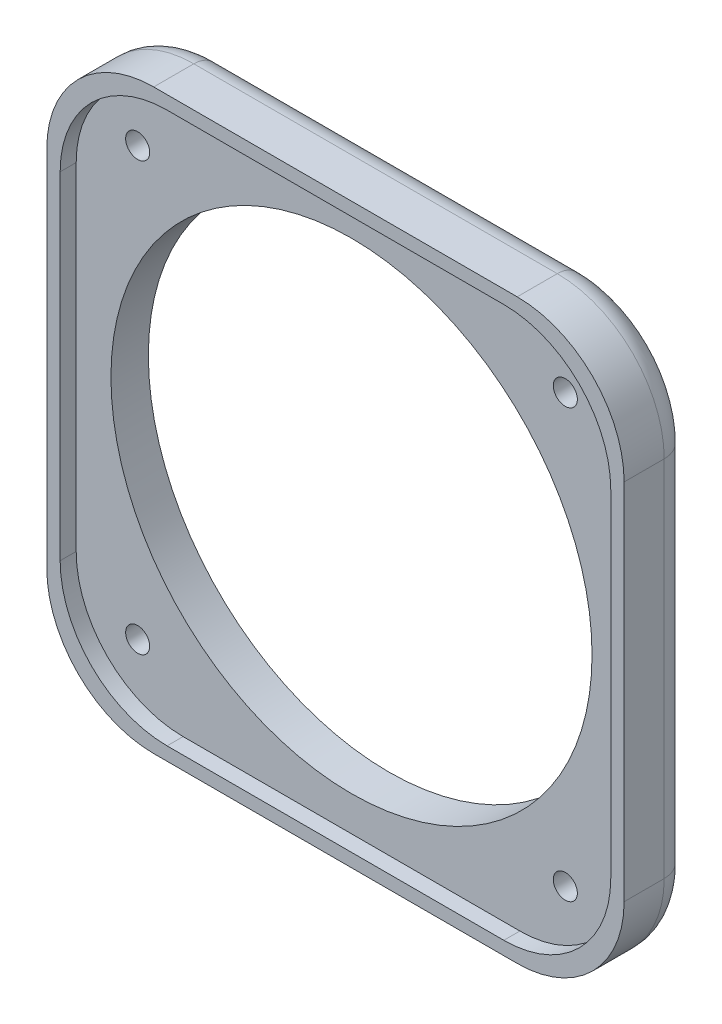
SolidWorks part; units mm, degrees
ref_plane "Plan de face" through (0, 0, 0) normal (0, 0, 1) x (1, 0, 0)
ref_plane "Plan de dessus" through (0, 0, 0) normal (0, 1, 0) x (1, 0, 0)
ref_plane "Plan de droite" through (0, 0, 0) normal (1, 0, 0) x (0, 0, -1)
sketch "Esquisse1" plane through (0, 0, 0) normal (0, 0, 1) x (1, 0, 0)
  line L1 (20, 0) -> (88, 0)
  line L2 (0, -20) -> (0, -88)
  line L3 (20, -108) -> (88, -108)
  line L4 (108, -20) -> (108, -88)
  arc A0 (0, -88) -> (20, -108) centre (20, -88) ccw
  arc A1 (88, -108) -> (108, -88) centre (88, -88) ccw
  arc A2 (88, 0) -> (108, -20) centre (88, -20) cw
  arc A3 (20, 0) -> (0, -20) centre (20, -20) ccw
  circle A4 centre (54, -54) radius 45
  circle A5 centre (14, -14) radius 2.25
  circle A6 centre (94, -14) radius 2.25
  circle A7 centre (94, -94) radius 2.25
  circle A8 centre (14, -94) radius 2.25
  point P7 (0, -108)
  point P12 (108, 0)
  point P15 (0, 0)
  point P18 (54, 0)
  point P19 (108, -54)
  dimension "D3" = 20
  dimension "D4" = 90
  dimension "D7" = 4.5
  dimension "D8" = 4.5
  dimension "D9" = 4.5
  dimension "D10" = 4.5
  dimension "D1" = 108
  dimension "D2" = 108
  dimension "D5" = 54
  dimension "D6" = 54
  dimension "D11" = 80
  dimension "D12" = 80
  dimension "D13" = 80
  dimension "D14" = 80
  dimension "D15" = 14
  dimension "D16" = 14
  dimension "D17" = 14
  dimension "D18" = 14
  dimension "D19" = 14
  dimension "D20" = 14
extrude "Boss.-Extru.1" add sketch "Esquisse1" along normal blind 7
sketch "Esquisse2" plane through (0, 0, 7) normal (0, 0, 1) x (1, 0, 0)
  line L0 (108, -88) -> (108, -20) construction
  line L1 (20, 0) -> (88, 0)
  line L2 (0, -20) -> (0, -88)
  line L3 (20, -108) -> (88, -108)
  line L4 (108, -20) -> (108, -88)
  line L5 (20, -108) -> (88, -108) construction
  line L7 (22.5, -2.5) -> (85.5, -2.5)
  line L8 (2.5, -22.5) -> (2.5, -85.5)
  line L9 (22.5, -105.5) -> (85.5, -105.5)
  line L10 (105.5, -22.5) -> (105.5, -85.5)
  arc A0 (0, -88) -> (20, -108) centre (20, -88) ccw
  arc A1 (88, -108) -> (108, -88) centre (88, -88) ccw
  arc A2 (88, 0) -> (108, -20) centre (88, -20) cw
  arc A3 (20, 0) -> (0, -20) centre (20, -20) ccw
  arc A4 (2.5, -85.5) -> (22.5, -105.5) centre (22.5, -85.5) ccw
  arc A5 (85.5, -105.5) -> (105.5, -85.5) centre (85.5, -85.5) ccw
  arc A6 (105.5, -22.5) -> (85.5, -2.5) centre (85.5, -22.5) ccw
  arc A7 (22.5, -2.5) -> (2.5, -22.5) centre (22.5, -22.5) ccw
  point P17 (0, 0)
  dimension "D3" = 20
  dimension "D8" = 20
  dimension "D1" = 0
  dimension "D2" = 0
  dimension "D4" = 2.5
  dimension "D5" = 2.5
  dimension "D6" = 2.5
  dimension "D7" = 2.5
extrude "Boss.-Extru.2" add sketch "Esquisse2" along normal blind 3
sketch "Esquisse3" plane through (0, 0, 0) normal (0, 0, -1) x (-1, 0, 0)
  line L0 (-20, -108) -> (-88, -108) construction
  line L1 (-20, 0) -> (-88, 0)
  line L2 (0, -20) -> (0, -88)
  line L3 (-20, -108) -> (-88, -108)
  line L4 (-108, -20) -> (-108, -88)
  line L5 (-108, -88) -> (-108, -20) construction
  line L7 (-84, -104) -> (-24, -104)
  line L8 (-104, -84) -> (-104, -24)
  line L9 (-84, -4) -> (-24, -4)
  line L10 (-4, -84) -> (-4, -24)
  arc A0 (-24, -104) -> (-4, -84) centre (-24, -84) ccw
  arc A1 (-4, -24) -> (-24, -4) centre (-24, -24) ccw
  arc A2 (-84, -4) -> (-104, -24) centre (-84, -24) ccw
  arc A3 (-104, -84) -> (-84, -104) centre (-84, -84) ccw
  arc A4 (-20, -108) -> (0, -88) centre (-20, -88) ccw
  arc A5 (0, -20) -> (-20, 0) centre (-20, -20) ccw
  arc A6 (-88, 0) -> (-108, -20) centre (-88, -20) ccw
  arc A7 (-108, -88) -> (-88, -108) centre (-88, -88) ccw
  point P13 (-54, -104)
  point P14 (-54, -108)
  point P15 (-4, -54)
  point P16 (0, -54)
  point P29 (0, 0)
  dimension "D7" = 20
  dimension "D8" = 20
  dimension "D1" = 0
  dimension "D2" = 0
  dimension "D3" = 100
  dimension "D4" = 100
  dimension "D5" = 0
  dimension "D6" = 0
extrude "Boss.-Extru.3" add sketch "Esquisse3" along normal blind 2.5
fillet "Congé1" radius 5 4 edges at (102.1421, -102.1421, -2.5) (102.1421, -5.8579, -2.5) (5.8579, -5.8579, -2.5) (5.8579, -102.1421, -2.5)
